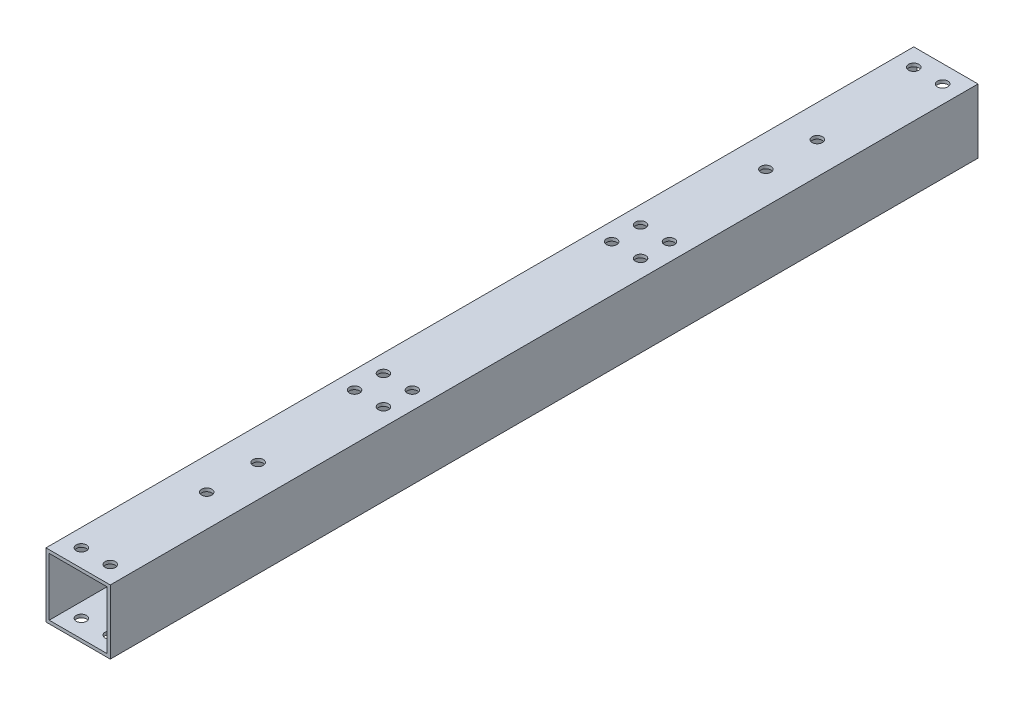
SolidWorks part; units mm, degrees
material "6061-T6 (SS)"
ref_plane "前视基准面" through (0, 0, 0) normal (0, 0, 1) x (1, 0, 0)
ref_plane "上视基准面" through (0, 0, 0) normal (0, 1, 0) x (1, 0, 0)
ref_plane "右视基准面" through (0, 0, 0) normal (1, 0, 0) x (0, 0, -1)
sketch "草图1" plane through (0, 0, 0) normal (0, 0, 1) x (1, 0, 0)
  line L1 (-10, 10) -> (10, 10)
  line L2 (-10, 10) -> (-10, -10)
  line L3 (-10, -10) -> (10, -10)
  line L4 (10, 10) -> (10, -10)
  line L5 (-10, 10) -> (10, -10) construction
  line L6 (-10, -10) -> (10, 10) construction
  line L7 (-9, 9) -> (9, 9)
  line L8 (-9, 9) -> (-9, -9)
  line L9 (-9, -9) -> (9, -9)
  line L10 (9, 9) -> (9, -9)
  line L11 (-9, 9) -> (9, -9) construction
  line L12 (-9, -9) -> (9, 9) construction
  point P0 (0, 0)
  point P6 (0, 0)
  dimension "D1" = 20
  dimension "D2" = 20
  dimension "D3" = 18
  dimension "D4" = 18
extrude "凸台-拉伸1" add sketch "草图1" along normal blind 270
sketch "草图2" plane through (0, 10, 0) normal (0, 1, 0) x (1, 0, 0)
  line L0 (0, -135) -> (78.9073, -135) construction
  line L1 (-10, 0) -> (10, 0) construction
  line L2 (-10, 0) -> (-10, -270) construction
  line L3 (-10, -270) -> (10, -270) construction
  line L4 (10, 0) -> (10, -270) construction
  line L5 (-10, 0) -> (10, -270) construction
  line L6 (-10, -270) -> (10, 0) construction
  line L7 (-10, -105) -> (10, -105) construction
  line L8 (-10, -105) -> (-10, -165) construction
  line L9 (-10, -165) -> (10, -165) construction
  line L10 (10, -105) -> (10, -165) construction
  line L11 (-10, -105) -> (10, -165) construction
  line L12 (-10, -165) -> (10, -105) construction
  line L13 (-10, -165) -> (10, -165) construction
  line L14 (-10, -165) -> (-10, -185) construction
  line L15 (-10, -185) -> (10, -185) construction
  line L16 (10, -165) -> (10, -185) construction
  line L17 (-10, -165) -> (10, -185) construction
  line L18 (-10, -185) -> (10, -165) construction
  line L20 (-4.5, -170.5) -> (4.5, -170.5) construction
  line L21 (-4.5, -170.5) -> (-4.5, -179.5) construction
  line L22 (-4.5, -179.5) -> (4.5, -179.5) construction
  line L23 (4.5, -170.5) -> (4.5, -179.5) construction
  line L24 (-4.5, -170.5) -> (4.5, -179.5) construction
  line L25 (-4.5, -179.5) -> (4.5, -170.5) construction
  circle A0 centre (-4.5, -179.5) radius 1.6
  circle A1 centre (4.5, -179.5) radius 1.6
  circle A2 centre (4.5, -170.5) radius 1.6
  circle A3 centre (-4.5, -170.5) radius 1.6
  circle A4 centre (-4.5, -99.5) radius 1.6
  circle A5 centre (4.5, -90.5) radius 1.6
  circle A6 centre (4.5, -99.5) radius 1.6
  circle A7 centre (-4.5, -90.5) radius 1.6
  point P4 (0, -135)
  point P7 (0, -135)
  point P14 (0, -175)
  point P16 (0, -175)
  dimension "D5" = 2
  dimension "D1" = 60
  dimension "D2" = 20
  dimension "D3" = 9
  dimension "D4" = 9
  dimension "D6" = 2
extrude "切除-拉伸1" cut sketch "草图2" against normal through all
sketch "草图3" plane through (0, -10, 0) normal (0, -1, 0) x (1, 0, 0)
  line L1 (-4.5, 90.5) -> (4.5, 90.5) construction
  line L2 (-4.5, 90.5) -> (-4.5, 99.5) construction
  line L3 (-4.5, 99.5) -> (4.5, 99.5) construction
  line L4 (4.5, 90.5) -> (4.5, 99.5) construction
  line L5 (-4.5, 90.5) -> (4.5, 99.5) construction
  line L6 (-4.5, 99.5) -> (4.5, 90.5) construction
  line L7 (-9, 104) -> (9, 104) construction
  line L8 (-9, 104) -> (-9, 86) construction
  line L9 (-9, 86) -> (9, 86) construction
  line L10 (9, 104) -> (9, 86) construction
  line L11 (-9, 104) -> (9, 86) construction
  line L12 (-9, 86) -> (9, 104) construction
  line L16 (-9.0089, 99.5) -> (-9, 90.2168)
  line L17 (-4.7832, 104) -> (4.5, 104.0089)
  line L18 (9, 99.7832) -> (9.0089, 90.5)
  line L19 (4.7832, 86) -> (-4.5, 85.9911)
  line L20 (9, 170.2168) -> (9.0089, 179.5)
  line L21 (-10, 270) -> (10, 270) construction
  line L22 (-10, 270) -> (-10, 0) construction
  line L23 (-10, 0) -> (10, 0) construction
  line L24 (10, 270) -> (10, 0) construction
  line L25 (0, 0) -> (0, 270) construction
  line L26 (-10, 135) -> (10, 135) construction
  line L27 (-4.7832, 166) -> (4.5, 165.9911)
  line L28 (-9.0089, 170.5) -> (-9, 179.7832)
  line L29 (4.7832, 184) -> (-4.5, 184.0089)
  circle A0 centre (-4.5, 90.5) radius 4.5 construction
  arc A1 (-9, 90.2168) -> (-4.5, 85.9911) centre (-4.5, 90.5) ccw
  arc A2 (-4.7832, 104) -> (-9.0089, 99.5) centre (-4.5, 99.5) ccw
  arc A3 (9, 99.7832) -> (4.5, 104.0089) centre (4.5, 99.5) ccw
  arc A4 (4.7832, 86) -> (9.0089, 90.5) centre (4.5, 90.5) ccw
  arc A5 (4.7832, 184) -> (9.0089, 179.5) centre (4.5, 179.5) cw
  arc A6 (9, 170.2168) -> (4.5, 165.9911) centre (4.5, 170.5) cw
  arc A7 (-4.7832, 166) -> (-9.0089, 170.5) centre (-4.5, 170.5) cw
  arc A8 (-9, 179.7832) -> (-4.5, 184.0089) centre (-4.5, 179.5) cw
  point P4 (0, 95)
  point P7 (0, 95)
  point P392 (0, 135)
  dimension "D1" = 18
  dimension "D2" = 18
  dimension "D4" = 4
extrude "切除-拉伸2" cut sketch "草图3" against normal up to surface (1 mm away) up to face at (-4.5, -9, 172.1)
sketch "草图4" plane through (0, 10, 0) normal (0, 1, 0) x (1, 0, 0)
  line L0 (-10, -270) -> (-10, 0) construction
  line L1 (-10, 0) -> (10, 0) construction
  line L2 (-10, 0) -> (-10, -20) construction
  line L3 (-10, -20) -> (10, -20) construction
  line L4 (10, 0) -> (10, -20) construction
  line L5 (-10, 0) -> (10, -20) construction
  line L6 (-10, -20) -> (10, 0) construction
  line L7 (10, -270) -> (10, 0) construction
  line L9 (-4.5, -5.5) -> (4.5, -5.5) construction
  line L10 (-4.5, -5.5) -> (-4.5, -14.5) construction
  line L11 (-4.5, -14.5) -> (4.5, -14.5) construction
  line L12 (4.5, -5.5) -> (4.5, -14.5) construction
  line L13 (0, -14.5) -> (0, -5.5) construction
  line L14 (-4.5, -10) -> (4.5, -10) construction
  line L15 (-10, -270) -> (10, -270) construction
  line L16 (-10, -270) -> (-10, -250) construction
  line L17 (-10, -250) -> (10, -250) construction
  line L18 (10, -270) -> (10, -250) construction
  line L19 (-10, -270) -> (10, -250) construction
  line L20 (-10, -250) -> (10, -270) construction
  line L21 (-4.5, -255.5) -> (4.5, -255.5) construction
  line L22 (-4.5, -255.5) -> (-4.5, -264.5) construction
  line L23 (-4.5, -264.5) -> (4.5, -264.5) construction
  line L24 (4.5, -255.5) -> (4.5, -264.5) construction
  line L25 (0, -264.5) -> (0, -255.5) construction
  line L26 (-4.5, -260) -> (4.5, -260) construction
  circle A0 centre (-4.5, -5.5) radius 1.6
  circle A1 centre (4.5, -5.5) radius 1.6
  circle A2 centre (-4.5, -264.5) radius 1.6
  circle A3 centre (4.5, -264.5) radius 1.6
  point P4 (0, -10)
  point P9 (0, -10)
  point P19 (0, -260)
  point P20 (0, -260)
  dimension "D4" = 20
  dimension "D1" = 20
  dimension "D2" = 9
  dimension "D3" = 9
  dimension "D5" = 9
  dimension "D6" = 9
extrude "切除-拉伸3" cut sketch "草图4" against normal through all
sketch "草图5" plane through (0, -10, 0) normal (0, -1, 0) x (1, 0, 0)
  line L0 (10, 270) -> (10, 0) construction
  line L1 (-10, 0) -> (10, 0) construction
  line L2 (-10, 0) -> (-10, 40) construction
  line L3 (-10, 40) -> (10, 40) construction
  line L4 (10, 0) -> (10, 40) construction
  line L5 (0, 40) -> (0, 0) construction
  line L6 (-10, 20) -> (10, 20) construction
  line L8 (-10, 40) -> (10, 40) construction
  line L9 (-10, 40) -> (-10, 56) construction
  line L10 (-10, 56) -> (10, 56) construction
  line L11 (10, 40) -> (10, 56) construction
  line L12 (0, 56) -> (0, 40) construction
  line L13 (-10, 48) -> (10, 48) construction
  circle A0 centre (0, 56) radius 1.6
  circle A1 centre (0, 40) radius 1.6
  point P220 (0, 48)
  point P256 (0, 20)
  dimension "D1" = 40
  dimension "D2" = 16
extrude "切除-拉伸4" cut sketch "草图5" against normal through all
ref_plane "基准面1" through (0, 0, 135) normal (0, 0, -1) x (-1, 0, 0)
mirror "镜向1" about plane through (0, 0, 135) normal (0, 0, -1) of "切除-拉伸4"
sketch "草图6" plane through (0, -10, 0) normal (0, -1, 0) x (1, 0, 0)
  line L0 (0, 230) -> (0, 214) construction
  line L1 (6, 230) -> (6, 214)
  line L2 (-6, 230) -> (-6, 214)
  arc A0 (6, 230) -> (-6, 230) centre (0, 230) ccw
  arc A1 (-6, 214) -> (6, 214) centre (0, 214) ccw
  point P4 (0, 222)
extrude "切除-拉伸5" cut sketch "草图6" against normal up to next
mirror "镜向2" about plane through (0, 0, 135) normal (0, 0, -1) of "切除-拉伸5"
